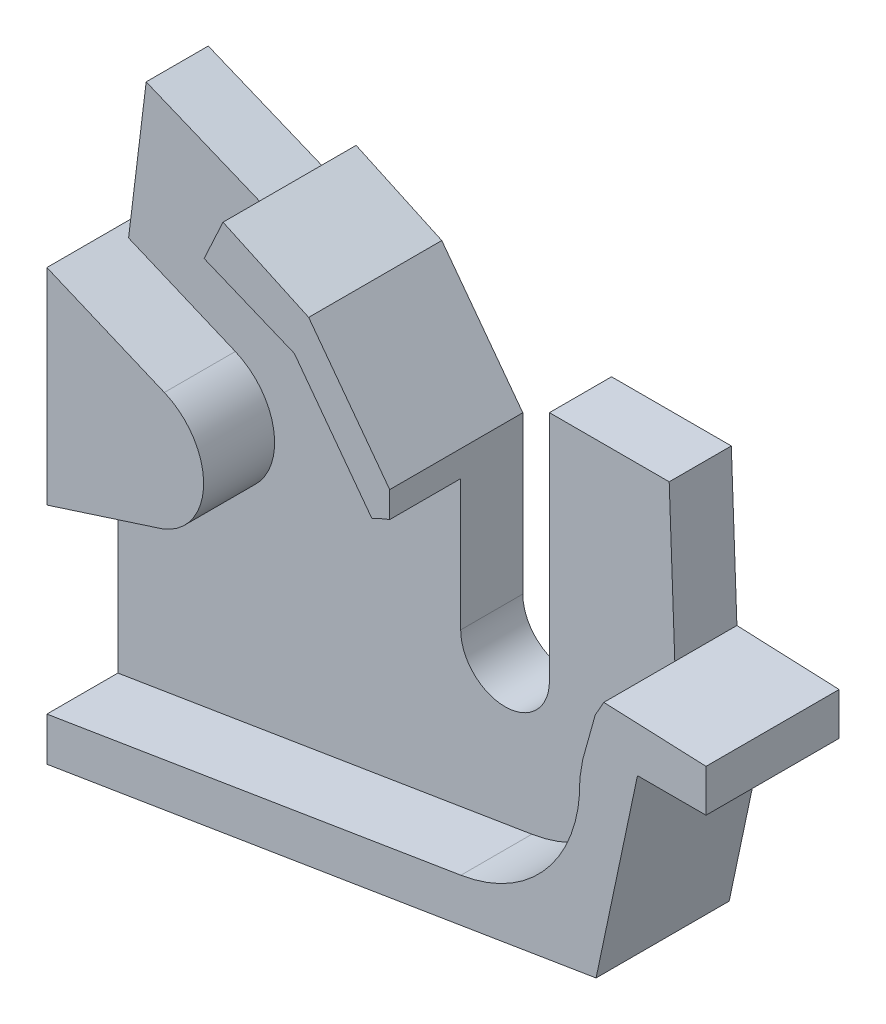
SolidWorks part; units mm, degrees
ref_plane "Front Plane" through (0, 0, 0) normal (0, 0, 1) x (1, 0, 0)
ref_plane "Top Plane" through (0, 0, 0) normal (0, 1, 0) x (1, 0, 0)
ref_plane "Right Plane" through (0, 0, 0) normal (1, 0, 0) x (0, 0, -1)
sketch "Sketch1" plane through (0, 0, 0) normal (0, 0, 1) x (1, 0, 0)
  line L0 (-48.8998, -64.1664) -> (-34.4801, 53.9567) construction
  line L3 (0, 51.4823) -> (78.4652, 51.4823)
  line L4 (78.4652, 0) -> (78.4652, 51.4823)
  line L5 (-0.9054, 14.8469) -> (9.0946, 14.8469)
  line L6 (9.0946, 14.8469) -> (9.0946, -2.1531)
  line L7 (9.0946, -2.1531) -> (-0.9054, -2.1531)
  line L8 (-0.9054, -2.1531) -> (-0.9054, 14.8469)
  line L9 (-11.6542, 28.4583) -> (-0.9054, 14.02)
  line L10 (-52.5896, 45.2866) -> (-11.6542, 28.4583)
  line L11 (9.0946, 14.8469) -> (9.0946, 29.052)
  line L12 (9.0946, 29.052) -> (22.5946, 29.052)
  line L13 (-61.5112, 32.1478) -> (-26.3036, 17.3197)
  line L14 (-26.3036, 17.3197) -> (-29.1124, 10.6505)
  line L15 (-29.1124, 10.6505) -> (-31.9213, 3.9813)
  line L16 (-70.304, -10.1797) -> (-26.4323, 3.9286)
  line L17 (-39.5424, 22.8954) -> (-39.5424, -0.2874)
  line L18 (-26.4323, 3.9286) -> (-29.1124, 10.6505)
  line L19 (-29.1124, 10.6505) -> (-31.7926, 17.3724)
  line L20 (-74.2907, -26.3461) -> (-1.036, -14.4136)
  line L21 (-1.036, -14.4136) -> (7.1186, -13.0853)
  line L22 (23.2246, 11.8381) -> (22.2572, 10.123)
  line L23 (23.2246, 11.8381) -> (34.7443, 11.3546)
  line L24 (-0.9054, 14.8469) -> (-0.9054, 20.5391)
  line L25 (-0.9054, 20.5391) -> (-7.2539, 29.052)
  line L26 (-7.2539, 29.052) -> (-10.0368, 32.7838)
  line L27 (-10.0368, 32.7838) -> (-19.6901, 37.2479)
  line L28 (-19.6901, 37.2479) -> (-21.8219, 32.6382)
  line L29 (-70.3938, -25.7113) -> (-69.6167, -30.4821)
  line L30 (-69.6167, -30.4821) -> (22.3519, -15.5013)
  line L31 (22.3519, -15.5013) -> (27.019, 6.583)
  line L32 (27.019, 6.583) -> (34.7443, 6.583)
  line L33 (34.7443, 6.583) -> (34.7443, 11.3546)
  line L34 (-11.6542, 28.4583) -> (-8.9222, 28.4583)
  line L35 (-70.3938, -25.7113) -> (-70.304, -10.1797)
  line L36 (22.5946, 29.052) -> (23.2246, 11.8381)
  line L37 (-39.5424, -0.2874) -> (-39.5424, -25.5833)
  line L38 (-39.5424, 22.8954) -> (-39.5424, 39.923)
  line L39 (22.2572, 10.123) -> (21.4546, 7.2463)
  line L40 (21.4546, 7.2463) -> (20.8501, 5.08)
  line L41 (20.8501, 5.08) -> (20.5233, 3.0772)
  line L42 (-8.9222, 28.4583) -> (-8.9222, 25.2921)
  circle A0 centre (4.0946, 2.8469) radius 5
  circle A1 centre (4.0946, 9.8469) radius 5
  circle A2 centre (-29.1124, 10.6505) radius 7.2365
  circle A3 centre (4.5907, 2.6512) radius 15.9383
  point P52 (0, 0)
  point P53 (0, 0)
  point P54 (-11.6542, 28.4583)
  point P55 (-39.5424, 39.923)
  point P56 (-15.5228, 26.2319)
  point P57 (-16.4681, 30.2095)
  point P58 (7.8486, -12.9612)
  point P59 (7.1186, -13.0853)
  dimension "D4" = 13.5
  dimension "D1" = 119
  dimension "D2" = 10
  dimension "D3" = 17
  dimension "D5" = 18
extrude "Boss-Extrude2" add sketch "Sketch1" along normal blind 7 contours L0 L13 A2 L16 L37 L20 L21 A3 L9 L10 | L0 L17 L16 A2 L13 | A3 L21 L20 L37 L30 L31 L32 L33 L23 L22 L39 L40 L41 | A3 L11 L6 L7 L8 L9 | A3 L41 L40 L39 L22 L36 L12 L11 | A3 L24 L25 L26 L27 L28 L10 L9 | L24 A3 L9 L8 | A0 L8 L7 | A0 L7 L6 | A2 region at (-38.7106, -23.1346, 0) region at (-22.3108, 6.082, 0) region at (-38.6776, 17.405, 0) region at (-10.092, -2.2905, 0) region at (-1.579, 16.1313, 0) region at (-10.6418, 28.2474, 0) region at (16.9061, 20.4045, 0) region at (0.2115, -1.0363, 0) region at (7.9778, -1.0363, 0)
extrude "Boss-Extrude3" add sketch "Sketch1<7>" along normal blind 15 contours L0 L16 A2 L13 | L19 A2 L15 | L16 L0 L13 L17 | L18 A2 L14 | L15 A2 L18 | L14 A2 L19 | A3 L24 L25 L26 L27 L28 L10 | A3 L21 L20 L37 L30 L31 L32 L33 L23 region at (-38.7106, -23.1346, 0) region at (-39.1396, 19.2563, 0) region at (-38.6776, 17.405, 0) region at (-29.1589, 5.9483, 0) region at (-25.3354, 10.6142, 0) region at (-29.0673, 15.3539, 0) region at (-32.8895, 10.6867, 0) region at (-10.6418, 28.2474, 0)
sketch "Sketch1<7>" plane through (0, 0, 0) normal (0, 0, 1) x (1, 0, 0) same geometry as "Sketch1"
